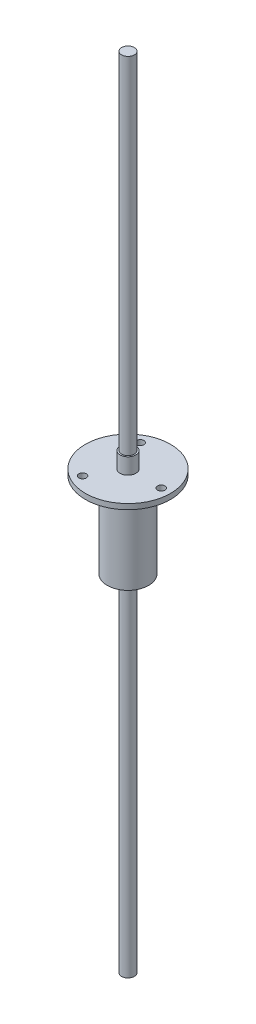
SolidWorks part; units mm, degrees
ref_plane "Front Plane" through (0, 0, 0) normal (0, 0, 1) x (1, 0, 0)
ref_plane "Top Plane" through (0, 0, 0) normal (0, 1, 0) x (1, 0, 0)
ref_plane "Right Plane" through (0, 0, 0) normal (1, 0, 0) x (0, 0, -1)
sketch "Sketch1" plane through (0, 0, 0) normal (1, 0, 0) x (0, 0, -1)
  line L0 (0, 23.9311) -> (0, -15.9842) construction
  line L1 (0, 20.05) -> (2.95, 20.05)
  line L2 (2.95, 20.05) -> (2.95, 14.05)
  line L3 (2.95, 14.05) -> (16, 14.05)
  line L4 (16, 14.05) -> (16, 12.05)
  line L5 (16, 12.05) -> (7.75, 12.05)
  line L6 (7.75, 12.05) -> (7.75, -20.05)
  line L7 (7.75, -20.05) -> (0, -20.05)
  line L8 (0, -20.05) -> (0, 20.05)
  dimension "D1" = 5.9
  dimension "D2" = 34.1
  dimension "D3" = 2
  dimension "D4" = 6
  dimension "D5" = 32
  dimension "D6" = 15.5
revolve "Revolve1" add sketch "Sketch1" angle 360 about L0
sketch "Sketch2" plane through (0, 14.05, 0) normal (0, 1, 0) x (1, 0, 0)
  circle A0 centre (0, 0) radius 12.5 construction
  circle A1 centre (12.5, 0) radius 1.4
  circle A2 centre (-6.25, -10.8253) radius 1.4
  circle A3 centre (-6.25, 10.8253) radius 1.4
  point P11 (0, 0)
  dimension "D1" = 3
  dimension "D2" = 25
  dimension "D3" = 2.8
extrude "Cut-Extrude1" cut sketch "Sketch2" against normal through all both
sketch "Sketch3" plane through (0, 0, 0) normal (0, 1, 0) x (1, 0, 0)
  circle A0 centre (0, 0) radius 2.4
  dimension "D1" = 4.8
extrude "Boss-Extrude1" add sketch "Sketch3" along normal mid plane 300
split "Split1" bodies to split 103 resulting bodies 104 105 split by face at (12.5, 14.05, 1.4)
